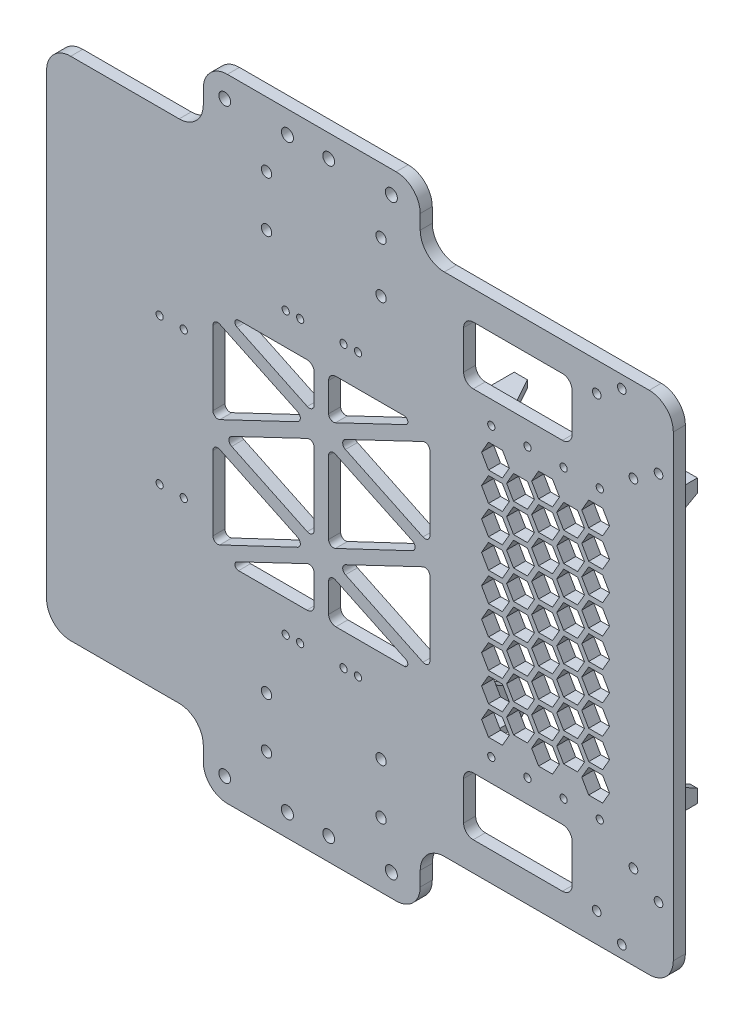
SolidWorks part; units mm, degrees
ref_plane "前视基准面" through (0, 0, 0) normal (0, 0, 1) x (1, 0, 0)
ref_plane "上视基准面" through (0, 0, 0) normal (0, 1, 0) x (1, 0, 0)
ref_plane "右视基准面" through (0, 0, 0) normal (1, 0, 0) x (0, 0, -1)
sketch "草图1" plane through (0, 0, 0) normal (0, 0, 1) x (1, 0, 0)
  line L2 (-130, 95) -> (-130, -95)
  line L3 (-120, -105) -> (-75, -105)
  line L4 (130, 95) -> (130, -95)
  line L5 (126.7518, 102.3765) -> (130, 105) construction
  line L6 (-130, -105) -> (-126.7518, -102.3765) construction
  line L9 (-65, -115) -> (-65, -121)
  line L10 (-55, -131) -> (15, -131)
  line L11 (25, -121) -> (25, -115)
  line L13 (35, -105) -> (120, -105)
  line L14 (126.7518, -102.3765) -> (130, -105) construction
  line L15 (-130, 105) -> (-126.7518, 102.3765) construction
  line L16 (-130, 0) -> (130, 0) construction
  line L17 (35, 105) -> (120, 105)
  line L18 (25, 121) -> (25, 115)
  line L19 (-55, 131) -> (15, 131)
  line L20 (-65, 115) -> (-65, 121)
  line L21 (-120, 105) -> (-75, 105)
  arc A1 (-120, -105) -> (-130, -95) centre (-120, -95) cw
  arc A3 (120, -105) -> (130, -95) centre (120, -95) ccw
  arc A8 (-65, -115) -> (-75, -105) centre (-75, -115) ccw
  arc A9 (25, -115) -> (35, -105) centre (35, -115) cw
  arc A10 (-55, -131) -> (-65, -121) centre (-55, -121) cw
  arc A11 (15, -131) -> (25, -121) centre (15, -121) ccw
  arc A12 (15, 131) -> (25, 121) centre (15, 121) cw
  arc A13 (-55, 131) -> (-65, 121) centre (-55, 121) ccw
  arc A14 (25, 115) -> (35, 105) centre (35, 115) ccw
  arc A15 (-65, 115) -> (-75, 105) centre (-75, 115) cw
  arc A16 (120, 105) -> (130, 95) centre (120, 95) cw
  arc A17 (-120, 105) -> (-130, 95) centre (-120, 95) ccw
  point P0 (0, 0)
  point P40 (25, -105)
  point P45 (25, 105)
  dimension "D2" = 10
  dimension "D3" = 65
  dimension "D4" = 10
  dimension "D5" = 105
  dimension "D7" = 10
  dimension "D8" = 10
  dimension "D10" = 10
  dimension "D12" = 10
  dimension "D13" = 105
  dimension "D18" = 90
  dimension "D19" = 6
extrude "凸台-拉伸1" add sketch "草图1" along normal blind 5
sketch "草图4" plane through (0, 0, 0) normal (0, 0, -1) x (-1, 0, 0)
  line L0 (-39, -47.5) -> (-39, -58.5)
  line L1 (-39, -58.5) -> (-50, -58.5)
  line L2 (-50, -58.5) -> (-50, -55.5)
  line L3 (-50, -55.5) -> (-42, -55.5)
  line L4 (-42, -55.5) -> (-42, -47.5)
  line L5 (-42, -47.5) -> (-39, -47.5)
  line L6 (-130, 0) -> (-25.5592, 0) construction
  line L7 (-130, -95) -> (-130, 95) construction
  line L10 (-130, -95) -> (-130, 95) construction
  dimension "D1" = 11
  dimension "D2" = 11
  dimension "D3" = 3
  dimension "D4" = 3
  dimension "D5" = 80
  dimension "D7" = 55.5
extrude "凸台-拉伸2" add sketch "草图4" along normal blind 20
sketch "草图5" plane through (0, -58.5, 0) normal (0, -1, 0) x (1, 0, 0)
  line L0 (50, -10) -> (44.5, -20)
  line L1 (50, -20) -> (50, 0) construction
  line L2 (50, -20) -> (39, -20) construction
  line L3 (44.5, -20) -> (50, -20)
  line L4 (50, -20) -> (50, -10)
  dimension "D1" = 10
  dimension "D2" = 5.5
extrude "切除-拉伸3" cut sketch "草图5" against normal blind 10
sketch "草图6" plane through (39, 0, 0) normal (-1, 0, 0) x (0, 0, 1)
  line L0 (-20, -53) -> (-10, -47.5)
  line L1 (-20, -58.5) -> (-20, -47.5) construction
  line L2 (-20, -47.5) -> (0, -47.5) construction
  line L3 (-10, -47.5) -> (-20, -47.5)
  line L4 (-20, -47.5) -> (-20, -53)
  dimension "D1" = 10
  dimension "D2" = 5.5
extrude "切除-拉伸4" cut sketch "草图6" against normal blind 10
ref_plane "基准面2" through (77, 0, 0) normal (1, 0, 0) x (0, 0, -1)
mirror "镜向1" about plane through (77, 0, 0) normal (1, 0, 0) of "凸台-拉伸2", "切除-拉伸4", "切除-拉伸3"
mirror "镜向2" about plane through (0, 0, 0) normal (0, 1, 0) of "镜向1"
sketch "草图7" plane through (0, 0, 0) normal (0, 0, -1) x (-1, 0, 0)
  line L4 (-112, -55.5) -> (-104, -55.5) construction
  line L5 (-112, 47.5) -> (-112, 55.5) construction
  line L6 (-112, 55.5) -> (-104, 55.5) construction
  line L7 (-92.013, 36) -> (-94.8997, 41)
  line L8 (-94.8997, 41) -> (-100.6732, 41)
  line L9 (-100.6732, 41) -> (-103.56, 36)
  line L10 (-103.56, 36) -> (-100.6732, 31)
  line L11 (-100.6732, 31) -> (-94.8997, 31)
  line L12 (-94.8997, 31) -> (-92.013, 36)
  line L13 (-77.0019, 36) -> (-97.7865, 36) construction
  line L14 (-74.1151, 31) -> (-71.2284, 36)
  line L15 (-71.2284, 36) -> (-74.1151, 41)
  line L16 (-74.1151, 41) -> (-79.8886, 41)
  line L17 (-79.8886, 41) -> (-82.7754, 36)
  line L18 (-82.7754, 36) -> (-79.8886, 31)
  line L19 (-79.8886, 31) -> (-74.1151, 31)
  line L20 (-92.013, 24) -> (-94.8997, 29)
  line L21 (-93.1677, 30) -> (-90.2809, 25)
  line L22 (-90.2809, 25) -> (-84.5074, 25)
  line L23 (-84.5074, 25) -> (-81.6207, 30)
  line L24 (-81.6207, 30) -> (-84.5074, 35)
  line L25 (-84.5074, 35) -> (-90.2809, 35)
  line L26 (-90.2809, 35) -> (-93.1677, 30)
  line L27 (-84.5074, 37) -> (-81.6207, 42)
  line L28 (-81.6207, 42) -> (-84.5074, 47)
  line L29 (-84.5074, 47) -> (-90.2809, 47)
  line L30 (-90.2809, 47) -> (-93.1677, 42)
  line L31 (-93.1677, 42) -> (-90.2809, 37)
  line L32 (-90.2809, 37) -> (-84.5074, 37)
  line L33 (-79.8886, 43) -> (-74.1151, 43)
  line L34 (-74.1151, 43) -> (-71.2284, 48)
  line L35 (-71.2284, 48) -> (-74.1151, 53)
  line L36 (-74.1151, 53) -> (-79.8886, 53)
  line L37 (-79.8886, 53) -> (-82.7754, 48)
  line L38 (-82.7754, 48) -> (-79.8886, 43)
  line L39 (-94.8997, 43) -> (-92.013, 48)
  line L40 (-92.013, 48) -> (-94.8997, 53)
  line L41 (-94.8997, 53) -> (-100.6732, 53)
  line L42 (-100.6732, 53) -> (-103.56, 48)
  line L43 (-103.56, 48) -> (-100.6732, 43)
  line L44 (-100.6732, 43) -> (-94.8997, 43)
  line L45 (-72.3831, 42) -> (-69.4963, 37)
  line L46 (-69.4963, 37) -> (-63.7228, 37)
  line L47 (-63.7228, 37) -> (-60.8361, 42)
  line L48 (-60.8361, 42) -> (-63.7228, 47)
  line L49 (-63.7228, 47) -> (-69.4963, 47)
  line L50 (-69.4963, 47) -> (-72.3831, 42)
  line L51 (-94.8997, 29) -> (-100.6732, 29)
  line L52 (-100.6732, 29) -> (-103.56, 24)
  line L53 (-103.56, 24) -> (-100.6732, 19)
  line L54 (-100.6732, 19) -> (-94.8997, 19)
  line L55 (-94.8997, 19) -> (-92.013, 24)
  line L56 (-93.1677, 18) -> (-90.2809, 13)
  line L57 (-90.2809, 13) -> (-84.5074, 13)
  line L58 (-84.5074, 13) -> (-81.6207, 18)
  line L59 (-81.6207, 18) -> (-84.5074, 23)
  line L60 (-84.5074, 23) -> (-90.2809, 23)
  line L61 (-90.2809, 23) -> (-93.1677, 18)
  line L62 (-74.1151, 19) -> (-71.2284, 24)
  line L63 (-71.2284, 24) -> (-74.1151, 29)
  line L64 (-74.1151, 29) -> (-79.8886, 29)
  line L65 (-79.8886, 29) -> (-82.7754, 24)
  line L66 (-82.7754, 24) -> (-79.8886, 19)
  line L67 (-79.8886, 19) -> (-74.1151, 19)
  line L68 (-72.3831, 30) -> (-69.4963, 25)
  line L69 (-69.4963, 25) -> (-63.7228, 25)
  line L70 (-63.7228, 25) -> (-60.8361, 30)
  line L71 (-60.8361, 30) -> (-63.7228, 35)
  line L72 (-63.7228, 35) -> (-69.4963, 35)
  line L73 (-69.4963, 35) -> (-72.3831, 30)
  line L74 (-92.013, 12) -> (-94.8997, 17)
  line L75 (-94.8997, 17) -> (-100.6732, 17)
  line L76 (-100.6732, 17) -> (-103.56, 12)
  line L77 (-103.56, 12) -> (-100.6732, 7)
  line L78 (-100.6732, 7) -> (-94.8997, 7)
  line L79 (-94.8997, 7) -> (-92.013, 12)
  line L80 (-93.1677, 6) -> (-90.2809, 1)
  line L81 (-90.2809, 1) -> (-84.5074, 1)
  line L82 (-84.5074, 1) -> (-81.6207, 6)
  line L83 (-81.6207, 6) -> (-84.5074, 11)
  line L84 (-84.5074, 11) -> (-90.2809, 11)
  line L85 (-90.2809, 11) -> (-93.1677, 6)
  line L86 (-74.1151, 7) -> (-71.2284, 12)
  line L87 (-71.2284, 12) -> (-74.1151, 17)
  line L88 (-74.1151, 17) -> (-79.8886, 17)
  line L89 (-79.8886, 17) -> (-82.7754, 12)
  line L90 (-82.7754, 12) -> (-79.8886, 7)
  line L91 (-79.8886, 7) -> (-74.1151, 7)
  line L92 (-72.3831, 18) -> (-69.4963, 13)
  line L93 (-69.4963, 13) -> (-63.7228, 13)
  line L94 (-63.7228, 13) -> (-60.8361, 18)
  line L95 (-60.8361, 18) -> (-63.7228, 23)
  line L96 (-63.7228, 23) -> (-69.4963, 23)
  line L97 (-69.4963, 23) -> (-72.3831, 18)
  line L98 (-92.013, 0) -> (-94.8997, 5)
  line L99 (-94.8997, 5) -> (-100.6732, 5)
  line L100 (-100.6732, 5) -> (-103.56, 0)
  line L101 (-103.56, 0) -> (-100.6732, -5)
  line L102 (-100.6732, -5) -> (-94.8997, -5)
  line L103 (-94.8997, -5) -> (-92.013, 0)
  line L104 (-93.1677, -6) -> (-90.2809, -11)
  line L105 (-90.2809, -11) -> (-84.5074, -11)
  line L106 (-84.5074, -11) -> (-81.6207, -6)
  line L107 (-81.6207, -6) -> (-84.5074, -1)
  line L108 (-84.5074, -1) -> (-90.2809, -1)
  line L109 (-90.2809, -1) -> (-93.1677, -6)
  line L110 (-74.1151, -5) -> (-71.2284, 0)
  line L111 (-71.2284, 0) -> (-74.1151, 5)
  line L112 (-74.1151, 5) -> (-79.8886, 5)
  line L113 (-79.8886, 5) -> (-82.7754, 0)
  line L114 (-82.7754, 0) -> (-79.8886, -5)
  line L115 (-79.8886, -5) -> (-74.1151, -5)
  line L116 (-72.3831, 6) -> (-69.4963, 1)
  line L117 (-69.4963, 1) -> (-63.7228, 1)
  line L118 (-63.7228, 1) -> (-60.8361, 6)
  line L119 (-60.8361, 6) -> (-63.7228, 11)
  line L120 (-63.7228, 11) -> (-69.4963, 11)
  line L121 (-69.4963, 11) -> (-72.3831, 6)
  line L122 (-92.013, -12) -> (-94.8997, -7)
  line L123 (-94.8997, -7) -> (-100.6732, -7)
  line L124 (-100.6732, -7) -> (-103.56, -12)
  line L125 (-103.56, -12) -> (-100.6732, -17)
  line L126 (-100.6732, -17) -> (-94.8997, -17)
  line L127 (-94.8997, -17) -> (-92.013, -12)
  line L128 (-93.1677, -18) -> (-90.2809, -23)
  line L129 (-90.2809, -23) -> (-84.5074, -23)
  line L130 (-84.5074, -23) -> (-81.6207, -18)
  line L131 (-81.6207, -18) -> (-84.5074, -13)
  line L132 (-84.5074, -13) -> (-90.2809, -13)
  line L133 (-90.2809, -13) -> (-93.1677, -18)
  line L134 (-74.1151, -17) -> (-71.2284, -12)
  line L135 (-71.2284, -12) -> (-74.1151, -7)
  line L136 (-74.1151, -7) -> (-79.8886, -7)
  line L137 (-79.8886, -7) -> (-82.7754, -12)
  line L138 (-82.7754, -12) -> (-79.8886, -17)
  line L139 (-79.8886, -17) -> (-74.1151, -17)
  line L140 (-72.3831, -6) -> (-69.4963, -11)
  line L141 (-69.4963, -11) -> (-63.7228, -11)
  line L142 (-63.7228, -11) -> (-60.8361, -6)
  line L143 (-60.8361, -6) -> (-63.7228, -1)
  line L144 (-63.7228, -1) -> (-69.4963, -1)
  line L145 (-69.4963, -1) -> (-72.3831, -6)
  line L146 (-92.013, -24) -> (-94.8997, -19)
  line L147 (-94.8997, -19) -> (-100.6732, -19)
  line L148 (-100.6732, -19) -> (-103.56, -24)
  line L149 (-103.56, -24) -> (-100.6732, -29)
  line L150 (-100.6732, -29) -> (-94.8997, -29)
  line L151 (-94.8997, -29) -> (-92.013, -24)
  line L152 (-93.1677, -30) -> (-90.2809, -35)
  line L153 (-90.2809, -35) -> (-84.5074, -35)
  line L154 (-84.5074, -35) -> (-81.6207, -30)
  line L155 (-81.6207, -30) -> (-84.5074, -25)
  line L156 (-84.5074, -25) -> (-90.2809, -25)
  line L157 (-90.2809, -25) -> (-93.1677, -30)
  line L158 (-74.1151, -29) -> (-71.2284, -24)
  line L159 (-71.2284, -24) -> (-74.1151, -19)
  line L160 (-74.1151, -19) -> (-79.8886, -19)
  line L161 (-79.8886, -19) -> (-82.7754, -24)
  line L162 (-82.7754, -24) -> (-79.8886, -29)
  line L163 (-79.8886, -29) -> (-74.1151, -29)
  line L164 (-72.3831, -18) -> (-69.4963, -23)
  line L165 (-69.4963, -23) -> (-63.7228, -23)
  line L166 (-63.7228, -23) -> (-60.8361, -18)
  line L167 (-60.8361, -18) -> (-63.7228, -13)
  line L168 (-63.7228, -13) -> (-69.4963, -13)
  line L169 (-69.4963, -13) -> (-72.3831, -18)
  line L170 (-92.013, -36) -> (-94.8997, -31)
  line L171 (-94.8997, -31) -> (-100.6732, -31)
  line L172 (-100.6732, -31) -> (-103.56, -36)
  line L173 (-103.56, -36) -> (-100.6732, -41)
  line L174 (-100.6732, -41) -> (-94.8997, -41)
  line L175 (-94.8997, -41) -> (-92.013, -36)
  line L176 (-93.1677, -42) -> (-90.2809, -47)
  line L177 (-90.2809, -47) -> (-84.5074, -47)
  line L178 (-84.5074, -47) -> (-81.6207, -42)
  line L179 (-81.6207, -42) -> (-84.5074, -37)
  line L180 (-84.5074, -37) -> (-90.2809, -37)
  line L181 (-90.2809, -37) -> (-93.1677, -42)
  line L182 (-74.1151, -41) -> (-71.2284, -36)
  line L183 (-71.2284, -36) -> (-74.1151, -31)
  line L184 (-74.1151, -31) -> (-79.8886, -31)
  line L185 (-79.8886, -31) -> (-82.7754, -36)
  line L186 (-82.7754, -36) -> (-79.8886, -41)
  line L187 (-79.8886, -41) -> (-74.1151, -41)
  line L188 (-72.3831, -30) -> (-69.4963, -35)
  line L189 (-69.4963, -35) -> (-63.7228, -35)
  line L190 (-63.7228, -35) -> (-60.8361, -30)
  line L191 (-60.8361, -30) -> (-63.7228, -25)
  line L192 (-63.7228, -25) -> (-69.4963, -25)
  line L193 (-69.4963, -25) -> (-72.3831, -30)
  line L194 (-92.013, -48) -> (-94.8997, -43)
  line L195 (-94.8997, -43) -> (-100.6732, -43)
  line L196 (-100.6732, -43) -> (-103.56, -48)
  line L197 (-103.56, -48) -> (-100.6732, -53)
  line L198 (-100.6732, -53) -> (-94.8997, -53)
  line L199 (-94.8997, -53) -> (-92.013, -48)
  line L206 (-74.1151, -53) -> (-71.2284, -48)
  line L207 (-71.2284, -48) -> (-74.1151, -43)
  line L208 (-74.1151, -43) -> (-79.8886, -43)
  line L209 (-79.8886, -43) -> (-82.7754, -48)
  line L210 (-82.7754, -48) -> (-79.8886, -53)
  line L211 (-79.8886, -53) -> (-74.1151, -53)
  line L212 (-72.3831, -42) -> (-69.4963, -47)
  line L213 (-69.4963, -47) -> (-63.7228, -47)
  line L214 (-63.7228, -47) -> (-60.8361, -42)
  line L215 (-60.8361, -42) -> (-63.7228, -37)
  line L216 (-63.7228, -37) -> (-69.4963, -37)
  line L217 (-69.4963, -37) -> (-72.3831, -42)
  line L218 (-61.9908, 36) -> (-59.104, 31)
  line L219 (-61.9908, 48) -> (-59.104, 43)
  line L220 (-59.104, 43) -> (-53.3305, 43)
  line L221 (-53.3305, 43) -> (-50.4438, 48)
  line L222 (-50.4438, 48) -> (-53.3305, 53)
  line L223 (-53.3305, 53) -> (-59.104, 53)
  line L224 (-59.104, 53) -> (-61.9908, 48)
  line L225 (-59.104, 31) -> (-53.3305, 31)
  line L226 (-53.3305, 31) -> (-50.4438, 36)
  line L227 (-50.4438, 36) -> (-53.3305, 41)
  line L228 (-53.3305, 41) -> (-59.104, 41)
  line L229 (-59.104, 41) -> (-61.9908, 36)
  line L230 (-61.9908, 24) -> (-59.104, 19)
  line L231 (-59.104, 19) -> (-53.3305, 19)
  line L232 (-53.3305, 19) -> (-50.4438, 24)
  line L233 (-50.4438, 24) -> (-53.3305, 29)
  line L234 (-53.3305, 29) -> (-59.104, 29)
  line L235 (-59.104, 29) -> (-61.9908, 24)
  line L236 (-61.9908, 12) -> (-59.104, 7)
  line L237 (-59.104, 7) -> (-53.3305, 7)
  line L238 (-53.3305, 7) -> (-50.4438, 12)
  line L239 (-50.4438, 12) -> (-53.3305, 17)
  line L240 (-53.3305, 17) -> (-59.104, 17)
  line L241 (-59.104, 17) -> (-61.9908, 12)
  line L242 (-61.9908, 0) -> (-59.104, -5)
  line L243 (-59.104, -5) -> (-53.3305, -5)
  line L244 (-53.3305, -5) -> (-50.4438, 0)
  line L245 (-50.4438, 0) -> (-53.3305, 5)
  line L246 (-53.3305, 5) -> (-59.104, 5)
  line L247 (-59.104, 5) -> (-61.9908, 0)
  line L248 (-61.9908, -12) -> (-59.104, -17)
  line L249 (-59.104, -17) -> (-53.3305, -17)
  line L250 (-53.3305, -17) -> (-50.4438, -12)
  line L251 (-50.4438, -12) -> (-53.3305, -7)
  line L252 (-53.3305, -7) -> (-59.104, -7)
  line L253 (-59.104, -7) -> (-61.9908, -12)
  line L254 (-61.9908, -24) -> (-59.104, -29)
  line L255 (-59.104, -29) -> (-53.3305, -29)
  line L256 (-53.3305, -29) -> (-50.4438, -24)
  line L257 (-50.4438, -24) -> (-53.3305, -19)
  line L258 (-53.3305, -19) -> (-59.104, -19)
  line L259 (-59.104, -19) -> (-61.9908, -24)
  line L260 (-61.9908, -36) -> (-59.104, -41)
  line L261 (-59.104, -41) -> (-53.3305, -41)
  line L262 (-53.3305, -41) -> (-50.4438, -36)
  line L263 (-50.4438, -36) -> (-53.3305, -31)
  line L264 (-53.3305, -31) -> (-59.104, -31)
  line L265 (-59.104, -31) -> (-61.9908, -36)
  line L266 (-61.9908, -48) -> (-59.104, -53)
  line L267 (-59.104, -53) -> (-53.3305, -53)
  line L268 (-53.3305, -53) -> (-50.4438, -48)
  line L269 (-50.4438, -48) -> (-53.3305, -43)
  line L270 (-53.3305, -43) -> (-59.104, -43)
  line L271 (-59.104, -43) -> (-61.9908, -48)
  line L272 (-93.1677, -54) -> (-90.2809, -59) [skipped]
  line L273 (-90.2809, -59) -> (-84.5074, -59) [skipped]
  line L274 (-84.5074, -59) -> (-81.6207, -54) [skipped]
  line L275 (-81.6207, -54) -> (-84.5074, -49) [skipped]
  line L276 (-84.5074, -49) -> (-90.2809, -49) [skipped]
  line L277 (-90.2809, -49) -> (-93.1677, -54) [skipped]
  circle A0 centre (-97.7865, 36) radius 5 construction
  circle A1 centre (-77.0019, 36) radius 5 construction
  circle A2 centre (-87.3942, 30) radius 5 construction
  circle A3 centre (-87.3942, 42) radius 5 construction
  circle A4 centre (-77.0019, 48) radius 5 construction
  circle A5 centre (-97.7865, 48) radius 5 construction
  circle A6 centre (-66.6096, 42) radius 5 construction
  circle A7 centre (-56.2173, 48) radius 5 construction
  point P4 (-87.3942, 37)
  dimension "D1" = 2
  dimension "D3" = 10
  dimension "D4" = 10
  dimension "D5" = 2
  dimension "D7" = 10
  dimension "D11" = 10
  dimension "D14" = 10
  dimension "D15" = 10
  dimension "D20" = 10
  dimension "D2" = 2
  dimension "D6" = 2
  dimension "D8" = 2
  dimension "D9" = 2
  dimension "D10" = 2
  dimension "D12" = 2
  dimension "D13" = 2
  dimension "D16" = 2
  dimension "D17" = 2
  dimension "D19" = 2
  dimension "D21" = 9
  dimension "D22" = 2.5
  dimension "D23" = 2.5
  dimension "D24" = 8.44
  dimension "D18" = 8
extrude "切除-拉伸5" cut sketch "草图7" against normal blind 5
sketch "草图8" plane through (0, 0, 0) normal (0, 0, -1) x (-1, 0, 0)
  line L0 (-75.3677, 120) -> (-75.3677, -120)
  line L1 (-100.0285, 77.2863) -> (-100.0285, -77.2863)
  line L2 (-100.0285, 77.2863) -> (-75.3677, 120)
  line L3 (-100.0285, -77.2863) -> (-75.3677, -120)
  line L4 (-37.1297, 0) -> (-146.8562, 0) construction
  dimension "D1" = 30
  dimension "D2" = 30
  dimension "D3" = 120
  dimension "D4" = 120
sketch "草图9" plane through (0, 0, 0) normal (0, 0, -1) x (-1, 0, 0)
  line L0 (148.8518, 0) -> (-37.1297, 0) construction
  line L1 (-29, 41) -> (-29, 4)
  line L2 (-25, -45) -> (13, -45)
  line L3 (61, -41) -> (61, -4)
  line L4 (57, 45) -> (19, 45)
  line L14 (-29, 41) -> (9.8049, 22.5)
  line L15 (57, 0) -> (19, -18.1163)
  line L16 (130, 95) -> (130, -95) construction
  line L17 (63, 93) -> (118, 93)
  line L18 (63, 93) -> (63, 66)
  line L19 (63, 66) -> (118, 66)
  line L20 (118, 93) -> (118, 66)
  line L21 (75, 105) -> (120, 105) construction
  line L22 (63, -66) -> (118, -66)
  line L23 (118, -93) -> (118, -66)
  line L24 (63, -93) -> (118, -93)
  line L25 (63, -93) -> (63, -66)
  line L26 (-120, 105) -> (-35, 105) construction
  line L27 (-43, 93) -> (-88, 93)
  line L28 (-43, 93) -> (-43, 69)
  line L29 (-43, 69) -> (-88, 69)
  line L30 (-88, 93) -> (-88, 69)
  line L31 (-130, -95) -> (-130, 95) construction
  line L32 (-43, -69) -> (-88, -69)
  line L33 (-88, -93) -> (-88, -69)
  line L34 (-43, -93) -> (-88, -93)
  line L35 (-43, -93) -> (-43, -69)
  line L36 (-25, 45) -> (13, 26.8837)
  line L37 (-25, -45) -> (13, -26.8837)
  line L38 (61, 41) -> (22.0746, 22.5575)
  line L39 (-25.5359, 0) -> (13, -18.258)
  line L40 (57, 45) -> (19, 26.8837)
  line L41 (57, -45) -> (19, -26.8837)
  line L42 (16, 61.4977) -> (16, -60.5731) construction
  line L43 (13, 45) -> (13, 26.8837)
  line L44 (19, 45) -> (19, 26.8837)
  line L45 (13, 18.258) -> (13, -18.258)
  line L46 (9.8049, 22.5) -> (-29, 4)
  line L47 (19, 18.1163) -> (57, 0)
  line L48 (22.0746, 22.5575) -> (61, 4)
  line L49 (13, 18.258) -> (-25.5359, 0)
  line L50 (19, 18.1163) -> (19, -18.1163)
  line L51 (22.0746, -22.5575) -> (61, -41)
  line L52 (9.8049, -22.5) -> (-29, -41)
  line L53 (9.8049, -22.5) -> (-29, -4)
  line L54 (22.0746, -22.5575) -> (61, -4)
  line L55 (13, -26.8837) -> (13, -45)
  line L56 (19, -26.8837) -> (19, -45)
  line L57 (13, 45) -> (-25, 45)
  line L58 (-29, -4) -> (-29, -41)
  line L59 (19, -45) -> (57, -45)
  line L60 (61, 4) -> (61, 41)
  line L61 (-44, 41) -> (-44, -37.8122) construction
  dimension "D1" = 45
  dimension "D2" = 45
  dimension "D3" = 15
  dimension "D4" = 90
  dimension "D5" = 1
  dimension "D7" = 12
  dimension "D8" = 12
  dimension "D9" = 27
  dimension "D10" = 55
  dimension "D11" = 12
  dimension "D12" = 45
  dimension "D13" = 42
  dimension "D14" = 24
  dimension "D21" = 4
  dimension "D22" = 4
  dimension "D23" = 4
  dimension "D24" = 4
  dimension "D26" = 4
  dimension "D27" = 3
  dimension "D28" = 45
extrude "切除-拉伸6" cut sketch "草图9" against normal blind 5 contours L27 L30 L29 L28 | L34 L35 L32 L33 | L4 L44 L40 | L48 L60 L38 | L47 L50 L15 | L54 L51 L3 | L56 L59 L41 | L55 L37 L2 | L53 L58 L52 | L45 L49 L39 | L46 L14 L1 | L43 L57 L36 | L57 L36 L43 region at (16.065, 22.5, 0) region at (-0.3333, -38.9612, 0) region at (-48.0249, -22.5192, 0) region at (-31.6667, 38.9612, 0) region at (-31.6667, 0, 0) region at (65.5, 81, 0) region at (65.5, -81, 0) region at (-0.3333, 38.9612, 0) region at (-48.0249, 22.5192, 0) region at (-0.1547, 0, 0) region at (-31.6667, -38.9612, 0) region at (16.065, -22.5, 0)
fillet "圆角1" radius 4 8 edges at (43, -93, 2.5) (88, -69, 2.5) (43, -69, 2.5) (88, -93, 2.5) (88, 69, 2.5) (43, 69, 2.5) (43, 93, 2.5) (88, 93, 2.5)
fillet "圆角2" radius 1.5 4 edges at (25, -45, 2.5) (-57, -45, 2.5) (25, 45, 2.5) (-57, 45, 2.5)
fillet "圆角3" radius 2 22 edges at (29, -4, 2.5) (29, 4, 2.5) (-13, -18.258, 2.5) (-61, -41, 2.5) (-61, 4, 2.5) (-13, -26.8837, 2.5) (-13, 18.258, 2.5) (-61, -4, 2.5) (-22.0746, -22.5575, 2.5) (25.5359, 0, 2.5) (-22.0746, 22.5575, 2.5) (-61, 41, 2.5) (-19, 26.8837, 2.5) (-19, -26.8837, 2.5) (-19, -18.1163, 2.5) (29, -41, 2.5) (29, 41, 2.5) (-57, 0, 2.5) (-9.8049, -22.5, 2.5) (-13, 26.8837, 2.5) (-9.8049, 22.5, 2.5) (-19, 18.1163, 2.5)
fillet "圆角4" radius 3 4 edges at (-13, -45, 2.5) (-13, 45, 2.5) (-19, -45, 2.5) (-19, 45, 2.5)
sketch "草图10" plane through (0, 0, 0) normal (0, 0, -1) x (-1, 0, 0)
  line L0 (-37.1297, 0) -> (-146.8562, 0) construction
  line L1 (-37.1297, 0) -> (-146.8562, 0) construction
  circle A0 centre (-123.8743, 76.9597) radius 1.8 construction
  circle A1 centre (-113.4687, 70.0334) radius 1.8 construction
  circle A2 centre (-108.6364, 99.852) radius 1.8 construction
  circle A3 centre (-98.2308, 92.9256) radius 1.8 construction
  circle A7 centre (-8.75, 83.1665) radius 2.15 construction
  circle A8 centre (38.75, 83.1665) radius 2.15 construction
  circle A9 centre (38.75, 104.1665) radius 2.15 construction
  circle A10 centre (-8.75, 104.1665) radius 2.15 construction
  circle A11 centre (-13.0267, 121.679) radius 2.5 construction
  circle A12 centre (56.0941, 121.679) radius 2.45 construction
  circle A13 centre (30.0941, 121.679) radius 2.5 construction
  circle A14 centre (12.9733, 121.679) radius 2.45 construction
  circle A15 centre (-123.8743, 76.9597) radius 1.8
  circle A16 centre (-113.4687, 70.0334) radius 1.8
  circle A17 centre (-108.6364, 99.852) radius 1.8
  circle A18 centre (-98.2308, 92.9256) radius 1.8
  circle A26 centre (-13.0267, 121.679) radius 2.5
  circle A27 centre (56.0941, 121.679) radius 2.45
  circle A28 centre (30.0941, 121.679) radius 2.5
  circle A29 centre (12.9733, 121.679) radius 2.45
  circle A30 centre (12.9733, -121.679) radius 2.45
  circle A31 centre (30.0941, -121.679) radius 2.5
  circle A32 centre (56.0941, -121.679) radius 2.45
  circle A33 centre (-13.0267, -121.679) radius 2.5
  circle A41 centre (-98.2308, -92.9256) radius 1.8
  circle A42 centre (-108.6364, -99.852) radius 1.8
  circle A43 centre (-113.4687, -70.0334) radius 1.8
  circle A44 centre (-123.8743, -76.9597) radius 1.8
  circle A45 centre (-99.5, 59.5) radius 1.5 construction
  circle A46 centre (-84.5, 59.5) radius 1.5 construction
  circle A47 centre (-69.5, 59.5) radius 1.5 construction
  circle A48 centre (-54.5, 59.5) radius 1.5 construction
  circle A49 centre (0.8061, 58.25) radius 1.5 construction
  circle A50 centre (6.8061, 58.25) radius 1.5 construction
  circle A51 centre (24.8061, 58.25) radius 1.5 construction
  circle A52 centre (30.8061, 58.25) radius 1.5 construction
  circle A53 centre (-99.5, 59.5) radius 1.5
  circle A54 centre (-84.5, 59.5) radius 1.5
  circle A55 centre (-69.5, 59.5) radius 1.5
  circle A56 centre (-54.5, 59.5) radius 1.5
  circle A57 centre (0.8061, 58.25) radius 1.5
  circle A58 centre (6.8061, 58.25) radius 1.5
  circle A59 centre (24.8061, 58.25) radius 1.5
  circle A60 centre (30.8061, 58.25) radius 1.5
  circle A61 centre (30.8061, -58.25) radius 1.5
  circle A62 centre (24.8061, -58.25) radius 1.5
  circle A63 centre (6.8061, -58.25) radius 1.5
  circle A64 centre (0.8061, -58.25) radius 1.5
  circle A65 centre (-54.5, -59.5) radius 1.5
  circle A66 centre (-69.5, -59.5) radius 1.5
  circle A67 centre (-84.5, -59.5) radius 1.5
  circle A68 centre (-99.5, -59.5) radius 1.5
  circle A81 centre (-8.75, 83.1665) radius 2.15
  circle A82 centre (38.75, 83.1665) radius 2.15
  circle A83 centre (38.75, 104.1665) radius 2.15
  circle A84 centre (-8.75, 104.1665) radius 2.15
  circle A85 centre (-8.75, -104.1665) radius 2.15
  circle A86 centre (38.75, -104.1665) radius 2.15
  circle A87 centre (38.75, -83.1665) radius 2.15
  circle A88 centre (-8.75, -83.1665) radius 2.15
  circle A89 centre (73.1015, 30.3) radius 1.5 construction
  circle A90 centre (83.1015, 30.3) radius 1.5 construction
  circle A91 centre (73.1015, 30.3) radius 1.5
  circle A92 centre (83.1015, 30.3) radius 1.5
  circle A93 centre (83.1015, -30.3) radius 1.5
  circle A94 centre (73.1015, -30.3) radius 1.5
extrude "切除-拉伸7" cut sketch "草图10" against normal through all
equation "\"45、\"=43.7672"
